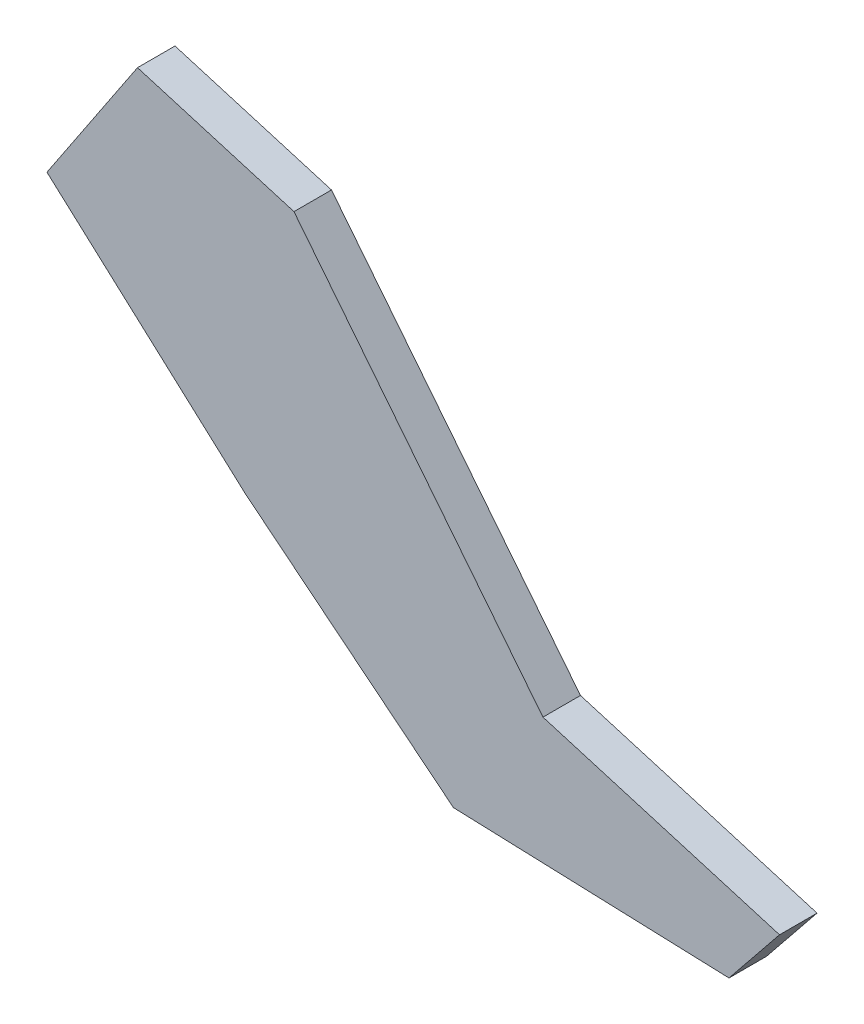
SolidWorks part; units mm, degrees
ref_plane "Front Plane" through (0, 0, 0) normal (0, 0, 1) x (1, 0, 0)
ref_plane "Top Plane" through (0, 0, 0) normal (0, 1, 0) x (1, 0, 0)
ref_plane "Right Plane" through (0, 0, 0) normal (1, 0, 0) x (0, 0, -1)
sketch "Sketch1" plane through (0, 0, 0) normal (0, 0, 1) x (1, 0, 0)
  line L0 (732.8355, 222.864) -> (759.3238, 215.0048)
  line L1 (759.3238, 215.0048) -> (801.4698, 161.9673)
  line L2 (801.4698, 161.9673) -> (841.5161, 150.0854)
  line L3 (841.5161, 150.0854) -> (832.9608, 139.4737)
  line L4 (832.9608, 139.4737) -> (786.3162, 141.1311)
  line L5 (786.3162, 141.1311) -> (751.1114, 169.5137)
  line L6 (751.1114, 169.5137) -> (717.5089, 199.8742)
  line L7 (717.5089, 199.8742) -> (732.8355, 222.864)
extrude "Boss-Extrude1" add sketch "Sketch1" along normal blind 3.175 and the other way blind 3.175 contours L1 L2 L3 L4 L5 L6 L7 L0
